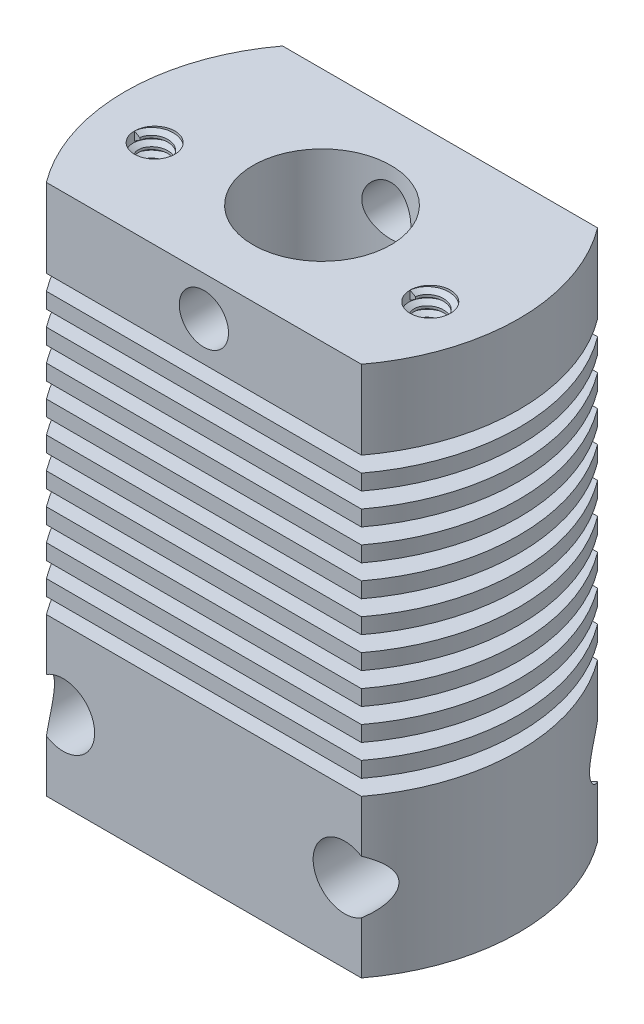
SolidWorks part; units mm, degrees
ref_plane "Alzado" through (0, 0, 0) normal (0, 0, 1) x (1, 0, 0)
ref_plane "Planta" through (0, 0, 0) normal (0, 1, 0) x (1, 0, 0)
ref_plane "Vista lateral" through (0, 0, 0) normal (1, 0, 0) x (0, 0, -1)
sketch "Croquis1" plane through (0, 0, 0) normal (0, 1, 0) x (1, 0, 0)
  line L1 (-10, -6) -> (10, -6)
  line L2 (-10, -6) -> (-10, 6)
  line L3 (-10, 6) -> (10, 6)
  line L4 (10, -6) -> (10, 6)
  line L5 (-10, -6) -> (10, 6) construction
  line L6 (-10, 6) -> (10, -6) construction
  circle A0 centre (0, 0) radius 3.5
  point P0 (0, 0)
  dimension "D3" = 7
  dimension "D1" = 20
  dimension "D2" = 12
extrude "Saliente-Extruir1" add sketch "Croquis1" along normal blind 27
sketch "Croquis3" plane through (0, 27, 0) normal (0, 1, 0) x (1, 0, 0)
  line L0 (10, -6) -> (10, 6) construction
  circle A0 centre (0, 0) radius 10
extrude "Cortar-Extruir-Lámina1" cut sketch "Croquis3" against normal blind 27 thin
sketch "Croquis5" plane through (0, 0, 6) normal (0, 0, 1) x (1, 0, 0)
  line L0 (-10, 23) -> (-4.3, 23)
  line L1 (-10, 27) -> (-10, 0) construction
  line L2 (-4.3, 23) -> (-4.3, 22.2106)
  line L3 (-4.3, 22.2106) -> (-10, 22.2106)
  line L4 (-10, 22.2106) -> (-10, 23)
  line L5 (-8, 27) -> (8, 27) construction
  line L7 (4.3, 23) -> (10, 23)
  line L8 (10, 23) -> (10, 22.2106)
  line L9 (10, 22.2106) -> (4.3, 22.2106)
  line L10 (4.3, 22.2106) -> (4.3, 23)
  line L11 (4.3, 21.42) -> (10, 21.42)
  line L12 (10, 21.42) -> (10, 20.6306)
  line L13 (10, 20.6306) -> (4.3, 20.6306)
  line L14 (4.3, 20.6306) -> (4.3, 21.42)
  line L15 (4.3, 19.84) -> (10, 19.84)
  line L16 (10, 19.84) -> (10, 19.0506)
  line L17 (10, 19.0506) -> (4.3, 19.0506)
  line L18 (4.3, 19.0506) -> (4.3, 19.84)
  line L19 (4.3, 18.26) -> (10, 18.26)
  line L20 (10, 18.26) -> (10, 17.4706)
  line L21 (10, 17.4706) -> (4.3, 17.4706)
  line L22 (4.3, 17.4706) -> (4.3, 18.26)
  line L23 (4.3, 16.68) -> (10, 16.68)
  line L24 (10, 16.68) -> (10, 15.8906)
  line L25 (10, 15.8906) -> (4.3, 15.8906)
  line L26 (4.3, 15.8906) -> (4.3, 16.68)
  line L27 (4.3, 15.1) -> (10, 15.1)
  line L28 (10, 15.1) -> (10, 14.3106)
  line L29 (10, 14.3106) -> (4.3, 14.3106)
  line L30 (4.3, 14.3106) -> (4.3, 15.1)
  line L31 (4.3, 13.52) -> (10, 13.52)
  line L32 (10, 13.52) -> (10, 12.7306)
  line L33 (10, 12.7306) -> (4.3, 12.7306)
  line L34 (4.3, 12.7306) -> (4.3, 13.52)
  line L35 (4.3, 11.94) -> (10, 11.94)
  line L36 (10, 11.94) -> (10, 11.1506)
  line L37 (10, 11.1506) -> (4.3, 11.1506)
  line L39 (4.3, 11.1506) -> (4.3, 11.94)
  line L40 (4.3, 10.36) -> (10, 10.36)
  line L41 (10, 10.36) -> (10, 9.5706)
  line L42 (10, 9.5706) -> (4.3, 9.5706)
  line L43 (4.3, 9.5706) -> (4.3, 10.36)
  line L45 (4.3, 8.78) -> (10, 8.78)
  line L46 (10, 8.78) -> (10, 7.9906)
  line L47 (10, 7.9906) -> (4.3, 7.9906)
  line L48 (4.3, 7.9906) -> (4.3, 8.78)
  line L49 (-10, 21.42) -> (-4.3, 21.42)
  line L50 (-4.3, 21.42) -> (-4.3, 20.6306)
  line L51 (-4.3, 20.6306) -> (-10, 20.6306)
  line L52 (-10, 20.6306) -> (-10, 21.42)
  line L53 (-10, 19.84) -> (-4.3, 19.84)
  line L54 (-4.3, 19.84) -> (-4.3, 19.0506)
  line L55 (-4.3, 19.0506) -> (-10, 19.0506)
  line L56 (-10, 19.0506) -> (-10, 19.84)
  line L57 (-10, 18.26) -> (-4.3, 18.26)
  line L58 (-4.3, 18.26) -> (-4.3, 17.4706)
  line L59 (-4.3, 17.4706) -> (-10, 17.4706)
  line L60 (-10, 17.4706) -> (-10, 18.26)
  line L61 (-10, 16.68) -> (-4.3, 16.68)
  line L62 (-4.3, 16.68) -> (-4.3, 15.8906)
  line L63 (-4.3, 15.8906) -> (-10, 15.8906)
  line L64 (-10, 15.8906) -> (-10, 16.68)
  line L65 (-10, 15.1) -> (-4.3, 15.1)
  line L66 (-4.3, 15.1) -> (-4.3, 14.3106)
  line L67 (-4.3, 14.3106) -> (-10, 14.3106)
  line L68 (-10, 14.3106) -> (-10, 15.1)
  line L69 (-10, 13.52) -> (-4.3, 13.52)
  line L70 (-4.3, 13.52) -> (-4.3, 12.7306)
  line L71 (-4.3, 12.7306) -> (-10, 12.7306)
  line L72 (-10, 12.7306) -> (-10, 13.52)
  line L73 (-10, 11.94) -> (-4.3, 11.94)
  line L74 (-4.3, 11.94) -> (-4.3, 11.1506)
  line L75 (-4.3, 11.1506) -> (-10, 11.1506)
  line L76 (-10, 11.1506) -> (-10, 11.94)
  line L77 (-10, 10.36) -> (-4.3, 10.36)
  line L78 (-4.3, 10.36) -> (-4.3, 9.5706)
  line L79 (-4.3, 9.5706) -> (-10, 9.5706)
  line L80 (-10, 9.5706) -> (-10, 10.36)
  line L81 (-10, 8.78) -> (-4.3, 8.78)
  line L82 (-4.3, 8.78) -> (-4.3, 7.9906)
  line L83 (-4.3, 7.9906) -> (-10, 7.9906)
  line L84 (-10, 7.9906) -> (-10, 8.78)
  dimension "D1" = 5.7
  dimension "D2" = 4
  dimension "D3" = 0.7894
  dimension "D5" = 10
  dimension "D4" = 2
extrude "Cortar-Extruir2" cut sketch "Croquis5" against normal blind 27
thread "Rosca1" [suppressed] pitch 1 start angle 0, offset 0, length 0, pitch 1, diameter 7
ref_plane "Plano1" through (3.5, 0, 0) normal (0, 0, 1) x (1, 0, 0)
sketch "Perfil de rosca1" plane through (3.5, 0, 0) normal (0, 0, 1) x (1, 0, 0)
  line L0 (0, 0) -> (0, 1) construction
  line L11 (0, 0) -> (0, 0.875)
  line L12 (0, 0.875) -> (-0.5413, 0.5625)
  line L13 (-0.5413, 0.5625) -> (-0.5413, 0.3125)
  line L15 (-0.5413, 0.3125) -> (0, 0)
  line L17 (-0.5413, 0.4375) -> (0, 0.4375) construction
  point P2 (0, 0)
  dimension "Pitch" = 1
  dimension "Profile_Angle" = 60
  dimension "Profile_Land" = 0.25
  dimension "Profile_Height" = 0.5413
sketch "Croquis4" plane through (0, 0, 6) normal (0, 0, 1) x (1, 0, 0)
  line L0 (-8, 0) -> (8, 0) construction
  line L1 (-8, 27) -> (8, 27) construction
  circle A0 centre (-7.15, 4) radius 1.6
  circle A1 centre (7.15, 4) radius 1.6
  circle A2 centre (0, 25) radius 1.25
  dimension "D1" = 3.2
  dimension "D2" = 14.3
  dimension "D5" = 2.5
  dimension "D3" = 4
  dimension "D4" = 7.15
  dimension "D6" = 2
extrude "Cortar-Extruir1" cut sketch "Croquis4" against normal blind 27
sketch "Croquis8" plane through (0, 27, 0) normal (0, 1, 0) x (1, 0, 0)
  circle A0 centre (-7, -1.5) radius 1.025
  circle A1 centre (7, -1.5) radius 1.025
  dimension "D1" = 14
  dimension "D3" = 2.05
  dimension "D2" = 7
  dimension "D4" = 1.5
extrude "Cortar-Extruir3" cut sketch "Croquis8" against normal blind 5
thread "Rosca2" pitch 0.5 start angle 0, offset 0, length 0, pitch 0.5, diameter 2.05
ref_plane "Plano2" through (-8.025, 27, 1.5) normal (0, 0, 1) x (-1, 0, 0)
sketch "Perfil de rosca2" plane through (-8.025, 27, 1.5) normal (0, 0, 1) x (-1, 0, 0)
  line L0 (0, 0) -> (0, 0.5) construction
  line L11 (0, 0) -> (0, 0.4375)
  line L12 (0, 0.4375) -> (-0.2706, 0.2812)
  line L13 (-0.2706, 0.2812) -> (-0.2706, 0.1562)
  line L15 (-0.2706, 0.1562) -> (0, 0)
  line L17 (-0.2706, 0.2187) -> (0, 0.2187) construction
  point P2 (0, 0)
  dimension "Pitch" = 0.5
  dimension "Profile_Angle" = 60
  dimension "Profile_Land" = 0.125
  dimension "Profile_Height" = 0.2706
thread "Rosca3" pitch 0.5 profile "Perfil de rosca3" start angle 0, offset 0, length 0, pitch 0.5, diameter 2.05
ref_plane "Plano3" through (5.975, 27, 1.5) normal (0, 0, 1) x (-1, 0, 0)
sketch "Perfil de rosca3" plane through (5.975, 27, 1.5) normal (0, 0, 1) x (-1, 0, 0)
  line L0 (0, 0) -> (0, 0.5) construction
  line L11 (0, 0) -> (0, 0.4375)
  line L12 (0, 0.4375) -> (-0.2706, 0.2812)
  line L13 (-0.2706, 0.2812) -> (-0.2706, 0.1562)
  line L15 (-0.2706, 0.1562) -> (0, 0)
  line L17 (-0.2706, 0.2187) -> (0, 0.2187) construction
  point P2 (0, 0)
  dimension "Pitch" = 0.5
  dimension "Profile_Angle" = 60
  dimension "Profile_Land" = 0.125
  dimension "Profile_Height" = 0.2706
sketch "Croquis9" plane through (0, 23, 0) normal (0, -1, 0) x (1, 0, 0)
  circle A0 centre (0, 0) radius 4.4
  dimension "D1" = 8.8
extrude "Cortar-Extruir-Lámina2" cut sketch "Croquis9" along normal up to surface (0.7894 mm away) thin
sketch "Croquis10" plane through (0, 0, 0) normal (0, 0, 1) x (1, 0, 0)
  line L0 (0, 0) -> (0, 27) construction
  line L1 (8, 0) -> (-8, 0) construction
  line L2 (8, 27) -> (-8, 27) construction
  line L3 (4.3, 22.2106) -> (4.3, 23)
  line L4 (8, 23) -> (-8, 23) construction
  line L5 (-4.3, 23) -> (4.3, 23) construction
  line L6 (4.3, 23) -> (10, 23)
  line L7 (10, 23) -> (10, 22.2106)
  line L8 (10, 22.2106) -> (8, 22.2106) construction
  line L9 (10, 22.2106) -> (4.3, 22.2106)
  line L10 (4.3, 21.42) -> (10, 21.42)
  line L11 (4.3, 20.6306) -> (4.3, 21.42)
  line L12 (10, 20.6306) -> (4.3, 20.6306)
  line L13 (10, 21.42) -> (10, 20.6306)
  line L14 (4.3, 19.84) -> (10, 19.84)
  line L15 (4.3, 19.0506) -> (4.3, 19.84)
  line L16 (10, 19.0506) -> (4.3, 19.0506)
  line L17 (10, 19.84) -> (10, 19.0506)
  line L18 (4.3, 18.26) -> (10, 18.26)
  line L19 (4.3, 17.4706) -> (4.3, 18.26)
  line L20 (10, 17.4706) -> (4.3, 17.4706)
  line L21 (10, 18.26) -> (10, 17.4706)
  line L22 (4.3, 16.68) -> (10, 16.68)
  line L23 (4.3, 15.8906) -> (4.3, 16.68)
  line L24 (10, 15.8906) -> (4.3, 15.8906)
  line L25 (10, 16.68) -> (10, 15.8906)
  line L26 (4.3, 15.1) -> (10, 15.1)
  line L27 (4.3, 14.3106) -> (4.3, 15.1)
  line L28 (10, 14.3106) -> (4.3, 14.3106)
  line L29 (10, 15.1) -> (10, 14.3106)
  line L30 (4.3, 13.52) -> (10, 13.52)
  line L31 (4.3, 12.7306) -> (4.3, 13.52)
  line L32 (10, 12.7306) -> (4.3, 12.7306)
  line L33 (10, 13.52) -> (10, 12.7306)
  line L34 (4.3, 11.94) -> (10, 11.94)
  line L35 (4.3, 11.1506) -> (4.3, 11.94)
  line L36 (10, 11.1506) -> (4.3, 11.1506)
  line L37 (10, 11.94) -> (10, 11.1506)
  line L38 (4.3, 10.36) -> (10, 10.36)
  line L39 (4.3, 9.5706) -> (4.3, 10.36)
  line L40 (10, 9.5706) -> (4.3, 9.5706)
  line L41 (10, 10.36) -> (10, 9.5706)
  line L42 (4.3, 8.78) -> (10, 8.78)
  line L43 (4.3, 7.9906) -> (4.3, 8.78)
  line L44 (10, 7.9906) -> (4.3, 7.9906)
  line L45 (10, 8.78) -> (10, 7.9906)
  dimension "D1" = 10
revolve "Cortar-Revolución1" cut sketch "Croquis10" angle 360 about L0
